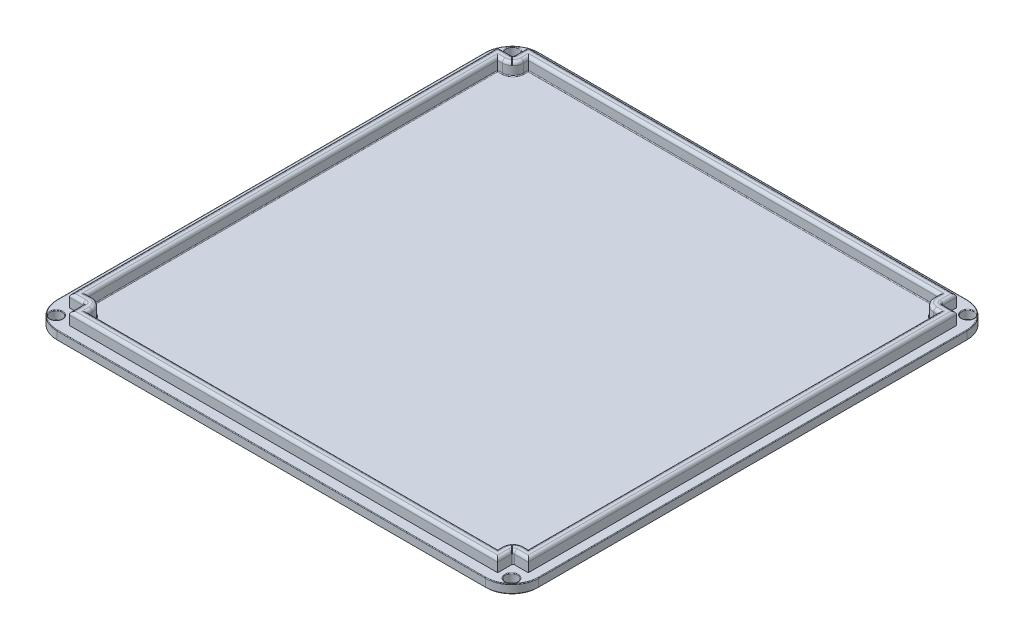
SolidWorks part; units mm, degrees
ref_plane "Front Plane" through (0, 0, 0) normal (0, 0, 1) x (1, 0, 0)
ref_plane "Top Plane" through (0, 0, 0) normal (0, 1, 0) x (1, 0, 0)
ref_plane "Right Plane" through (0, 0, 0) normal (1, 0, 0) x (0, 0, -1)
sketch "Sketch1" plane through (0, 0, 0) normal (0, 1, 0) x (1, 0, 0)
  line L8 (-70, -78.7) -> (70, -78.7)
  line L9 (78.7, -70) -> (78.7, 70)
  line L10 (70, 78.7) -> (-70, 78.7)
  line L11 (-78.7, 70) -> (-78.7, -70)
  line L12 (-70, 70) -> (70, -70) construction
  line L13 (70, -70) -> (70, 70) construction
  line L14 (70, 70) -> (-70, -70) construction
  arc A8 (-78.7, -70) -> (-70, -78.7) centre (-70, -70) ccw
  arc A9 (70, -78.7) -> (78.7, -70) centre (70, -70) ccw
  arc A10 (78.7, 70) -> (70, 78.7) centre (70, 70) ccw
  arc A11 (-70, 78.7) -> (-78.7, 70) centre (-70, 70) ccw
  point P13 (0, 0)
  dimension "D1" = 140
  dimension "D2" = 140
extrude "Boss-Extrude1" add sketch "Sketch1" along normal blind 3
sketch "Sketch2" plane through (0, 3, 0) normal (0, 1, 0) x (1, 0, 0)
  line L0 (-74.3691, 69.6926) -> (-74.3691, -70.3074)
  line L5 (-75, 75) -> (75, -75) construction
  line L6 (-75, -75) -> (75, 75) construction
  line L7 (-74.3691, -70.3074) -> (-69.8691, -70.3074)
  line L8 (-69.3691, -70.8074) -> (-69.3691, -75.3074)
  line L9 (-69.3691, -75.3074) -> (70.6309, -75.3074)
  line L10 (70.6309, -75.3074) -> (70.6309, -70.8074)
  line L11 (71.1309, -70.3074) -> (75.6309, -70.3074)
  line L12 (75.6309, -70.3074) -> (75.6309, 69.6926)
  line L13 (75.6309, 69.6926) -> (71.1309, 69.6926)
  line L14 (70.6309, 70.1926) -> (70.6309, 74.6926)
  line L15 (70.6309, 74.6926) -> (-69.3691, 74.6926)
  line L16 (-69.3691, 70.1926) -> (-69.3691, 74.6926)
  line L17 (-69.8691, 69.6926) -> (-74.3691, 69.6926)
  arc A4 (-69.5155, -70.4538) -> (-69.8691, -70.3074) centre (-69.8691, -70.8074) ccw
  arc A5 (-69.3691, -70.8074) -> (-69.5155, -70.4538) centre (-69.8691, -70.8074) ccw
  arc A6 (70.7774, -70.4538) -> (70.6309, -70.8074) centre (71.1309, -70.8074) ccw
  arc A7 (71.1309, -70.3074) -> (70.7774, -70.4538) centre (71.1309, -70.8074) ccw
  arc A8 (70.7774, 69.8391) -> (71.1309, 69.6926) centre (71.1309, 70.1926) ccw
  arc A9 (70.6309, 70.1926) -> (70.7774, 69.8391) centre (71.1309, 70.1926) ccw
  arc A10 (-69.8691, 69.6926) -> (-69.3691, 70.1926) centre (-69.8691, 70.1926) ccw
  point P0 (0, 0)
  dimension "D1" = 150
  dimension "D2" = 150
extrude "Extrude-Thin1" add sketch "Sketch2" along normal blind 4 thin thin type one direction reverse wall 3
fillet "Fillet1" radius 1 32 edges at (67.6309, 7, 71.5574) (70.6309, 7, 73.0574) (-71.3691, 7, 0.3074) (-70.6191, 7, 67.3074) (-67.3942, 7, 68.3325) (-66.3691, 7, 71.5574) (0.6309, 7, 72.3074) (68.6561, 7, 68.3325) (71.8809, 7, 67.3074) (72.6309, 7, 0.3074) (71.8809, 7, -66.6926) (68.6561, 7, -67.7178) (67.6309, 7, -70.9426) (0.6309, 7, -71.6926) (-66.3691, 7, -70.9426) (-67.3942, 7, -67.7178) (-70.6191, 7, -66.6926) (-69.5155, 7, -69.8391) (-69.3691, 7, -72.4426) (0.6309, 7, -74.6926) (70.6309, 7, -72.4426) (70.7774, 7, -69.8391) (73.3809, 7, -69.6926) (75.6309, 7, 0.3074) (73.3809, 7, 70.3074) (70.7774, 7, 70.4538) (0.6309, 7, 75.3074) (-69.3691, 7, 73.0574) (-69.5155, 7, 70.4538) (-72.1191, 7, 70.3074) (-74.3691, 7, 0.3074) (-72.1191, 7, -69.6926)
sketch "Sketch3" plane through (0, 7, 0) normal (0, 1, 0) x (1, 0, 0)
  line L0 (-75, 70) -> (-75, 75) construction
  line L1 (-70, 75) -> (-75, 75) construction
  line L2 (-75.0707, 74.9293) -> (-74.9293, 75.0707) construction
  line L3 (-75.0707, 74.9293) -> (78.5176, -78.659)
  line L4 (78.5176, -78.659) -> (78.659, -78.5176)
  line L5 (78.659, -78.5176) -> (-74.9293, 75.0707)
  line L6 (-74.9293, 75.0707) -> (-75.0707, 74.9293)
  point P1 (0, 0)
  point P10 (-75, 75)
  point P13 (0, 0)
  point P14 (0, 0)
  point P15 (0, 0)
extrude "Cut-Extrude1" cut sketch "Sketch3" against normal blind 3.8 draft 2.5
chamfer "Chamfer1" distance 0.3 angle 45 8 edges at (0, 0, 78.7) (76.1518, 0, 76.1518) (78.7, 0, 0) (76.1518, 0, -76.1518) (0, 0, -78.7) (-76.1518, 0, -76.1518) (-78.7, 0, 0) (-76.1518, 0, 76.1518)
sketch "Sketch4" plane through (0, 3, 0) normal (0, 1, 0) x (1, 0, 0)
  line L0 (-74.4012, 74.5642) -> (74.4012, -74.5642) construction
  line L1 (74.4012, -74.5642) -> (-74.4012, -74.5642) construction
  line L2 (-74.4012, -74.5642) -> (74.4012, 74.5642) construction
  circle A0 centre (-74.4012, 74.5642) radius 2
  circle A1 centre (74.4012, 74.5642) radius 2
  circle A2 centre (74.4012, -74.5642) radius 2
  circle A3 centre (-74.4012, -74.5642) radius 2
  point P8 (0, 0)
extrude "Cut-Extrude2" cut sketch "Sketch4" against normal blind 10
chamfer "Chamfer2" distance 0.2 angle 45 4 edges at (74.4012, 0, 76.5642) (-74.4012, 0, 76.5642) (74.4012, 0, -72.5642) (-74.4012, 0, -72.5642)
fillet "Fillet2" radius 0.2 12 edges at (-74.4012, 3, -72.5642) (-76.1518, 3, -76.1518) (-78.7, 3, 0) (-74.4012, 3, 76.5642) (-76.1518, 3, 76.1518) (0, 3, -78.7) (74.4012, 3, -72.5642) (76.1518, 3, -76.1518) (74.4012, 3, 76.5642) (0, 3, 78.7) (76.1518, 3, 76.1518) (78.7, 3, 0)
fillet "Fillet3" radius 0.25 16 edges at (-67.3942, 3, -67.7178) (-66.3691, 3, -70.9426) (0.6309, 3, -71.6926) (67.6309, 3, -70.9426) (68.6561, 3, -67.7178) (71.8809, 3, -66.6926) (72.6309, 3, 0.3074) (71.8809, 3, 67.3074) (68.6561, 3, 68.3325) (67.6309, 3, 71.5574) (0.6309, 3, 72.3074) (-66.3691, 3, 71.5574) (-67.3942, 3, 68.3325) (-70.6191, 3, 67.3074) (-71.3691, 3, 0.3074) (-70.6191, 3, -66.6926)
